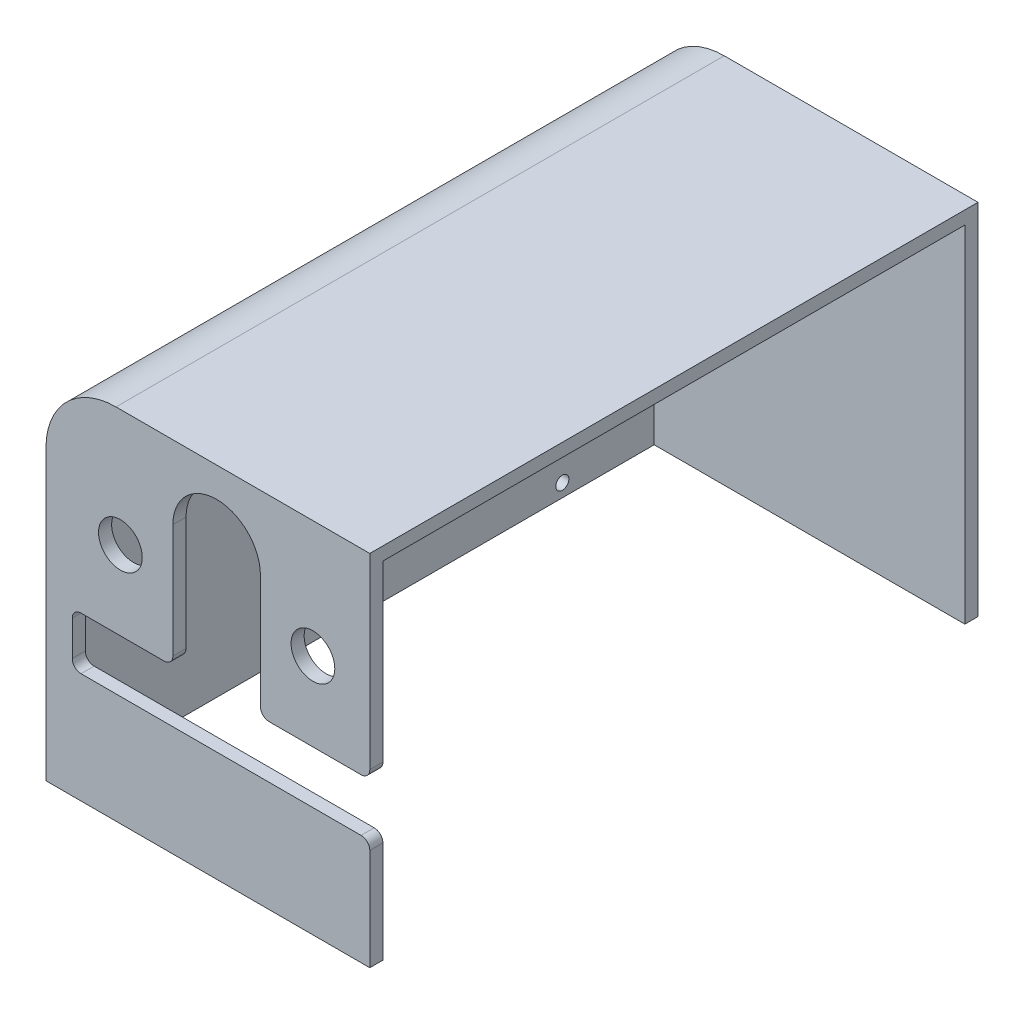
SolidWorks part; units mm, degrees
ref_plane "Front Plane" through (0, 0, 0) normal (0, 0, 1) x (1, 0, 0)
ref_plane "Top Plane" through (0, 0, 0) normal (0, 1, 0) x (1, 0, 0)
ref_plane "Right Plane" through (0, 0, 0) normal (1, 0, 0) x (0, 0, -1)
sketch "Sketch1" plane through (0, 0, 0) normal (0, 1, 0) x (1, 0, 0)
  line L0 (17.5, 35.5) -> (-18, 35.5)
  line L1 (-17.5, 35) -> (17.5, 35) construction
  line L2 (-17.5, 35) -> (-17.5, -35) construction
  line L3 (-17.5, -35) -> (17.5, -35) construction
  line L4 (17.5, 35) -> (17.5, -35) construction
  line L5 (-17.5, 35) -> (17.5, -35) construction
  line L6 (-17.5, -35) -> (17.5, 35) construction
  line L7 (-18, 35.5) -> (-18, -35.5)
  line L8 (-18, -35.5) -> (17.5, -35.5)
  line L9 (17.5, 37) -> (-19.5, 37)
  line L10 (-19.5, 37) -> (-19.5, -37)
  line L11 (-19.5, -37) -> (17.5, -37)
  line L12 (17.5, -35.5) -> (17.5, -37)
  line L13 (17.5, 37) -> (17.5, 35.5)
  point P0 (0, 0)
  dimension "D1" = 35
  dimension "D2" = 70
  dimension "D3" = 0.5
  dimension "D4" = 0.5
  dimension "D5" = 0.5
  dimension "D6" = 1.5
extrude "Boss-Extrude1" add sketch "Sketch1" along normal blind 26
sketch "Sketch2" plane through (0, 26, 0) normal (0, 1, 0) x (1, 0, 0)
  line L0 (-4, -27.5) -> (4, -27.5)
  line L1 (-19.5, -37) -> (28.4228, -37)
  line L2 (-19.5, -37) -> (-19.5, -32.5)
  line L3 (-19.5, -32.5) -> (28.4228, -32.5)
  line L4 (28.4228, -37) -> (28.4228, -32.5)
  line M5 (-19.5, 37) -> (-19.5, -37)
  line M6 (-19.5, -37) -> (17.5, -37)
  line M7 (17.5, -37) -> (17.5, -35.5)
  line M8 (17.5, -35.5) -> (-18, -35.5)
  line M9 (-18, -35.5) -> (-18, 35.5)
  dimension "D1" = 5
extrude "Cut-Extrude1" cut sketch "Sketch2" against normal through all both and the other way through all contours L1 L4 L3 M9 M8 M7 | L3 M5 M6 M7 M8 M9 region at (-2.3313, 26, 36.0812) region at (7.0798, 26, 34.2368)
sketch "Sketch3" plane through (0, 26, 0) normal (0, 1, 0) x (1, 0, 0)
  line L0 (17.5, 35.5) -> (17.5, 37) construction
  line L1 (-18, -32.5) -> (17.5, -32.5)
  line L2 (-18, -32.5) -> (-18, -31)
  line L3 (-18, -31) -> (17.5, -31)
  line L4 (17.5, -32.5) -> (17.5, -31)
  dimension "D1" = 1.5
extrude "Boss-Extrude2" add sketch "Sketch3" against normal up to vertex (26 mm away) up to point (-19.5, 0, 32.5)
sketch "Sketch4" plane through (0, 26, 0) normal (0, 1, 0) x (1, 0, 0)
  line L6 (-19.5, -32.5) -> (17.5, -32.5)
  line L11 (-18, -31) -> (-18, 35.5)
  line L12 (-18, 35.5) -> (17.5, 35.5)
  line L13 (17.5, 35.5) -> (17.5, 37)
  line L14 (17.5, 37) -> (-19.5, 37)
  line L15 (-19.5, 37) -> (-19.5, -32.5)
  line L19 (-18, -31) -> (-18, 35.5)
  line L20 (-18, 35.5) -> (17.5, 35.5)
  line L21 (17.5, 35.5) -> (17.5, 37)
  line L22 (17.5, 37) -> (-19.5, 37)
  line L23 (-19.5, 37) -> (-19.5, -32.5)
  line L31 (-19.5, -32.5) -> (17.5, -32.5)
  line L33 (17.5, -32.5) -> (17.5, -31)
  line L34 (17.5, -32.5) -> (17.5, -31)
  line L35 (17.5, -31) -> (-18, -31)
  line L36 (17.5, -31) -> (-18, -31)
  dimension "D1" = 0
extrude "Boss-Extrude3" add sketch "Sketch4" along normal blind 13.5
sketch "Sketch5" plane through (0, 39.5, 0) normal (0, 1, 0) x (1, 0, 0)
  line L1 (17.5, 37) -> (-19.5, 37)
  line L2 (17.5, 37) -> (17.5, -32.5)
  line L3 (17.5, -32.5) -> (-19.5, -32.5)
  line L4 (-19.5, 37) -> (-19.5, -32.5)
extrude "Boss-Extrude4" add sketch "Sketch5" along normal blind 1.5
fillet "Fillet1" radius 8 2 edges at (-18, 39.5, -2.25) (-19.5, 41, -2.25)
sketch "Sketch6" plane through (0, 0, 32.5) normal (0, 0, 1) x (1, 0, 0)
  line L0 (17.5, 0) -> (17.5, 41) construction
  line L5 (-16.5, 18.6) -> (17.5, 18.6)
  line L6 (-16.5, 18.6) -> (-16.5, 13.6)
  line L8 (17.5, 18.6) -> (17.5, 15.5285)
  line L9 (-5, 27.6) -> (-5, 32.6)
  line L10 (49.9164, 12.6) -> (17.5, 18.6) construction
  line L11 (-19.5, 0) -> (-19.5, 33) construction
  line L12 (-12.5, 12.6) -> (12.5, 12.6) construction
  line L13 (5, 18.6) -> (5, 27.6)
  line L14 (-5, 27.6) -> (-5, 18.6)
  line L15 (-11, 27.6) -> (11, 27.6) construction
  line L16 (-16.5, 13.6) -> (-16.5, 12.6)
  line L17 (-16.5, 12.6) -> (17.5, 12.6)
  line L18 (17.5, 12.6) -> (17.5, 15.5285)
  line L19 (-8.5, 14.6) -> (8.5, 14.6) construction
  line L20 (8.5, 14.6) -> (-8.5, 14.6) construction
  line L21 (-12.5, 16.6) -> (-8.5, 16.6) construction
  line L22 (-12.5, 16.6) -> (12.5, 16.6) construction
  line L23 (5, 32.6) -> (5, 27.6)
  circle A1 centre (-11, 27.6) radius 2.5
  circle A2 centre (11, 27.6) radius 2.5
  arc A3 (-5, 32.6) -> (5, 32.6) centre (0, 32.6) cw
  point P0 (49.9164, 12.6)
  point P23 (0, 27.6)
  line M9 (17.5, 0) -> (17.5, 41)
  dimension "D3" = 9
  dimension "D5" = 5
  dimension "D11" = 5
  dimension "D1" = 3
  dimension "D2" = 5
  dimension "D4" = 9
  dimension "D6" = 22
  dimension "D7" = 2
  dimension "D8" = 2
  dimension "D9" = 5
  dimension "D10" = 5
  dimension "D12" = 9
extrude "Cut-Extrude2" cut sketch "Sketch6" against normal blind 1.5 contours L13 L14 L5 | L6 L5 M9 | A2 | A1 region at (0.5, 15.6, 32.5) region at (0, 27.5982, 32.5) region at (-11, 27.6, 32.5) region at (11, 27.6, 32.5)
fillet "Fillet2" radius 1 6 edges at (17.5, 18.6, 31.75) (-16.5, 18.6, 31.75) (5, 18.6, 31.75) (-5, 18.6, 31.75) (17.5, 12.6, 31.75) (-16.5, 12.6, 31.75)
sketch "Sketch7" plane through (-19.5, 0, 0) normal (-1, 0, 0) x (0, 0, 1)
  circle A0 centre (25, 1.5) radius 0.75
  circle A1 centre (0, 1.5) radius 0.75
  circle A2 centre (-25, 1.5) radius 0.75
extrude "Cut-Extrude3" cut sketch "Sketch7" against normal through all both and the other way through all
